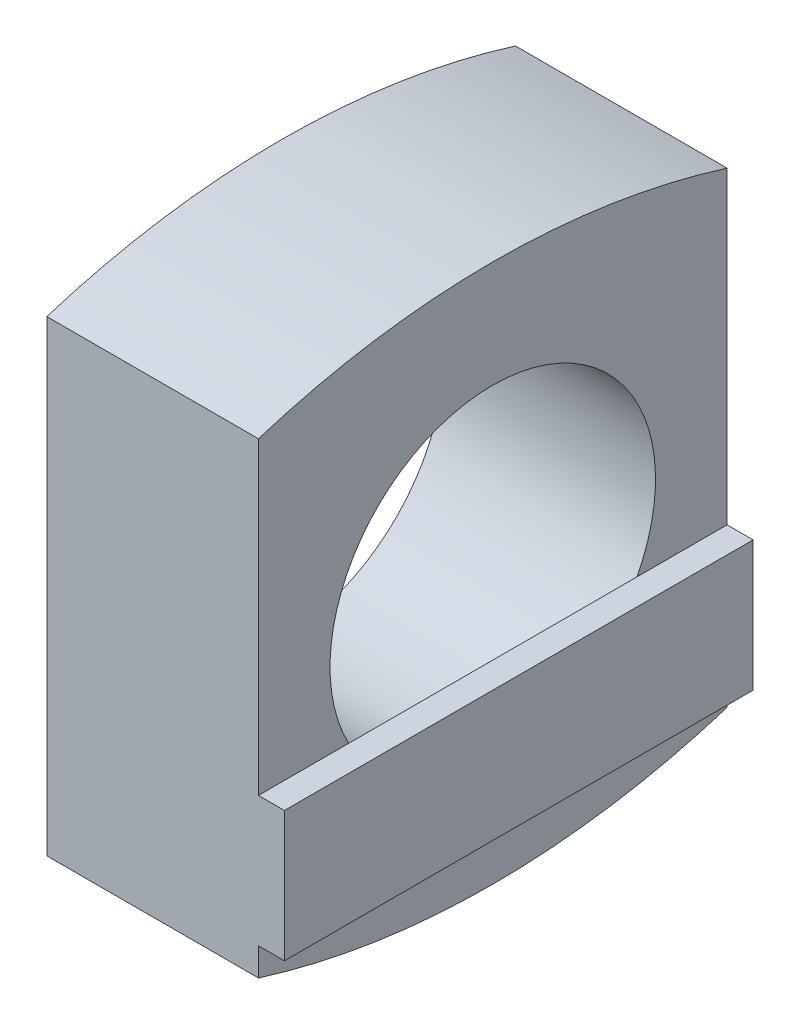
SolidWorks part; units mm, degrees
material "ABS"
ref_plane "Front Plane" through (0, 0, 0) normal (0, 0, 1) x (1, 0, 0)
ref_plane "Top Plane" through (0, 0, 0) normal (0, 1, 0) x (1, 0, 0)
ref_plane "Right Plane" through (0, 0, 0) normal (1, 0, 0) x (0, 0, -1)
sketch "Sketch2" plane through (0, 0, 0) normal (1, 0, 0) x (0, 0, -1)
  line L0 (60.6641, 0.9389) -> (106.3841, 0.9389)
  line L1 (60.6641, 0.9389) -> (60.6641, -21.8403)
  line L2 (106.3841, 0.9389) -> (106.3841, -21.8403)
  line L3 (67.6491, 0.9389) -> (99.3991, 0.9389)
  arc A0 (106.3841, -21.8403) -> (60.6641, -21.8403) centre (83.5241, 50.8499) cw
  arc A1 (67.6491, 0.9389) -> (99.3991, 0.9389) centre (83.5241, 0.9389) ccw
  point P8 (83.5241, -25.3501)
  dimension "D1" = 76.2
  dimension "D4" = 15.875
  dimension "D2" = 45.72
  dimension "D3" = 26.289
extrude "Boss-Extrude1" add sketch "Sketch2" along normal blind 20.6375 contours A0 L1 L0 L2
extrude "Cut-Extrude1" cut sketch "Sketch2<5>" along normal through all contours A1 L3
sketch "Sketch2<5>" plane through (0, 0, 0) normal (1, 0, 0) x (0, 0, -1) same geometry as "Sketch2"
mirror "Mirror4" about plane through (20.6375, 0.9389, -60.6641) normal (0, 1, 0) of "Boss-Extrude1"
mirror "Mirror5" about plane through (20.6375, 0.9389, -60.6641) normal (0, 1, 0) of "Cut-Extrude1"
sketch "Sketch3" plane through (20.6375, 0, 0) normal (1, 0, 0) x (0, 0, -1)
  line L0 (60.6641, 0.9389) -> (60.6641, -21.8403) construction
  line L1 (60.6641, -6.4161) -> (106.3841, -6.4161)
  line L2 (60.6641, -6.4161) -> (60.6641, -19.1161)
  line L3 (60.6641, -19.1161) -> (106.3841, -19.1161)
  line L4 (106.3841, -6.4161) -> (106.3841, -19.1161)
  line L5 (106.3841, 0.9389) -> (106.3841, -21.8403) construction
  dimension "D1" = 12.7
extrude "Boss-Extrude2" add sketch "Sketch3" along normal blind 2.54
